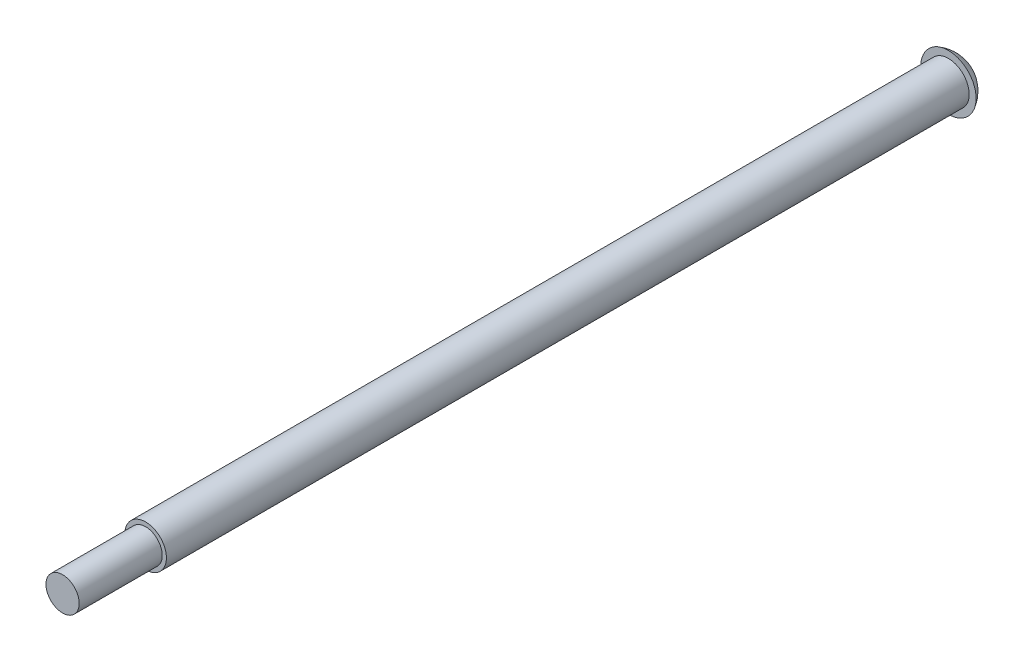
SolidWorks part; units mm, degrees
material "镀铬不锈钢"
ref_plane "前视基准面" through (0, 0, 0) normal (0, 0, 1) x (1, 0, 0)
ref_plane "上视基准面" through (0, 0, 0) normal (0, 1, 0) x (1, 0, 0)
ref_plane "右视基准面" through (0, 0, 0) normal (1, 0, 0) x (0, 0, -1)
sketch "草图1" plane through (0, 0, 0) normal (0, 0, 1) x (1, 0, 0)
  circle A0 centre (0, 0) radius 3
  dimension "D1" = 6
extrude "凸台-拉伸1" add sketch "草图1" along normal blind 160
sketch "草图2" plane through (0, 0, 0) normal (0, 1, 0) x (1, 0, 0)
  line L0 (0, 0) -> (5, 0)
  line L1 (0, 0) -> (0, 3)
  arc A0 (0, 3) -> (5, 0) centre (0, -2.6667) cw
  dimension "D1" = 5
  dimension "D2" = 3
revolve "旋转1" add sketch "草图2" angle 360 about L1
sketch "草图3" plane through (0, 0, 0) normal (0, 0, 1) x (1, 0, 0)
  circle A0 centre (0, 0) radius 3.75
  dimension "D1" = 7.5
extrude "凸台-拉伸2" add sketch "草图3" along normal offset from surface (145 mm away) 15 up to face at (3, 0, 160)
